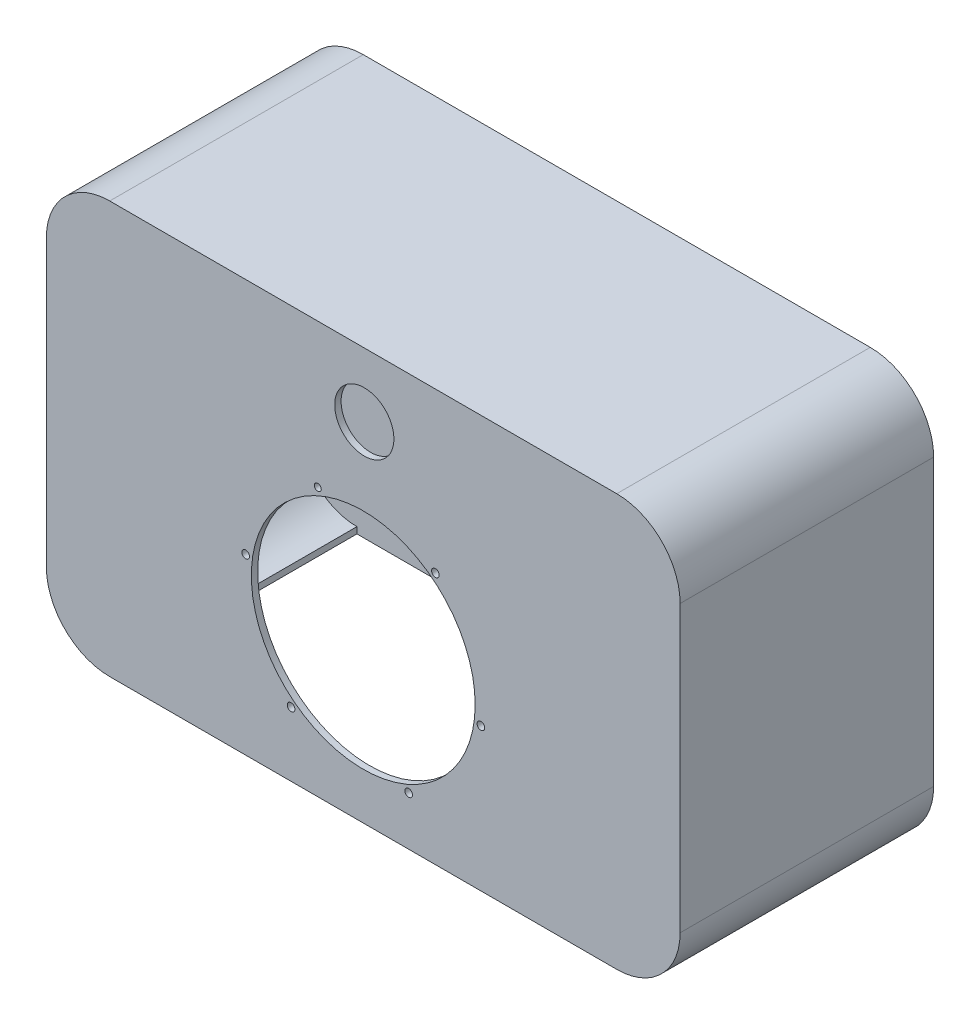
SolidWorks part; units mm, degrees
ref_plane "Plan de face" through (0, 0, 0) normal (0, 0, 1) x (1, 0, 0)
ref_plane "Plan de dessus" through (0, 0, 0) normal (0, 1, 0) x (1, 0, 0)
ref_plane "Plan de droite" through (0, 0, 0) normal (1, 0, 0) x (0, 0, -1)
sketch "Esquisse1" plane through (0, 0, 0) normal (0, 0, 1) x (1, 0, 0)
  line L1 (-40, 32.5) -> (40, 32.5)
  line L2 (-50, 22.5) -> (-50, -22.5)
  line L3 (-40, -32.5) -> (40, -32.5)
  line L4 (50, 22.5) -> (50, -22.5)
  line L5 (-50, 32.5) -> (50, -32.5) construction
  line L6 (-50, -32.5) -> (50, 32.5) construction
  arc A0 (40, -32.5) -> (50, -22.5) centre (40, -22.5) ccw
  arc A1 (-50, -22.5) -> (-40, -32.5) centre (-40, -22.5) ccw
  arc A2 (40, 32.5) -> (50, 22.5) centre (40, 22.5) cw
  arc A3 (-40, 32.5) -> (-50, 22.5) centre (-40, 22.5) ccw
  point P0 (0, 0)
  dimension "D2" = 10
  dimension "D1" = 100
  dimension "D3" = 45
extrude "Boss.-Extru.1" add sketch "Esquisse1" along normal blind 40
shell "Coque1" thickness 1 removed face at (0, -32.5, 20)
sketch "Esquisse2" plane through (0, 0, 40) normal (0, 0, 1) x (1, 0, 0)
  circle A0 centre (0.1686, 22.3939) radius 4.67
  circle A1 centre (0, -7.5) radius 17.6604
  circle A2 centre (-18.5578, -5.0643) radius 0.6038
  circle A3 centre (18.5578, -9.9357) radius 0.6038
  circle A4 centre (11.3883, 7.3537) radius 0.6038
  circle A5 centre (-7.1695, 9.7894) radius 0.5433
  circle A6 centre (7.1695, -24.7894) radius 0.6038
  circle A7 centre (-11.3883, -22.3537) radius 0.6038
extrude "Enlèv. mat.-Extru.1" cut sketch "Esquisse2" against normal blind 5
sketch "Esquisse3" plane through (0, -32.5, 0) normal (0, -1, 0) x (1, 0, 0)
  line L0 (-40, 1) -> (40, 1) construction
  line L1 (-12.5, -9) -> (12.5, -9)
  line L2 (-15, -6.5) -> (-15, 1)
  line L3 (-15, 1) -> (15, 1)
  line L4 (15, -6.5) -> (15, 1)
  line L5 (-15, -9) -> (15, 1) construction
  line L6 (-15, 1) -> (15, -9) construction
  line L7 (-15, -4) -> (15, -4) construction
  line L8 (0, -9) -> (0, 1) construction
  arc A0 (12.5, -9) -> (15, -6.5) centre (12.5, -6.5) ccw
  arc A1 (-12.5, -9) -> (-15, -6.5) centre (-12.5, -6.5) cw
  circle A2 centre (-10, -4) radius 1.5
  circle A3 centre (10, -4) radius 1.5
  point P0 (0, -4)
  dimension "D3" = 2.5
  dimension "D5" = 3
  dimension "D1" = 10
  dimension "D2" = 30
  dimension "D4" = 5
extrude "Boss.-Extru.2" add sketch "Esquisse3" against normal blind 5
fillet "Congé1" radius 5 2 edges at (15, -30, 0) (-15, -30, 0)
